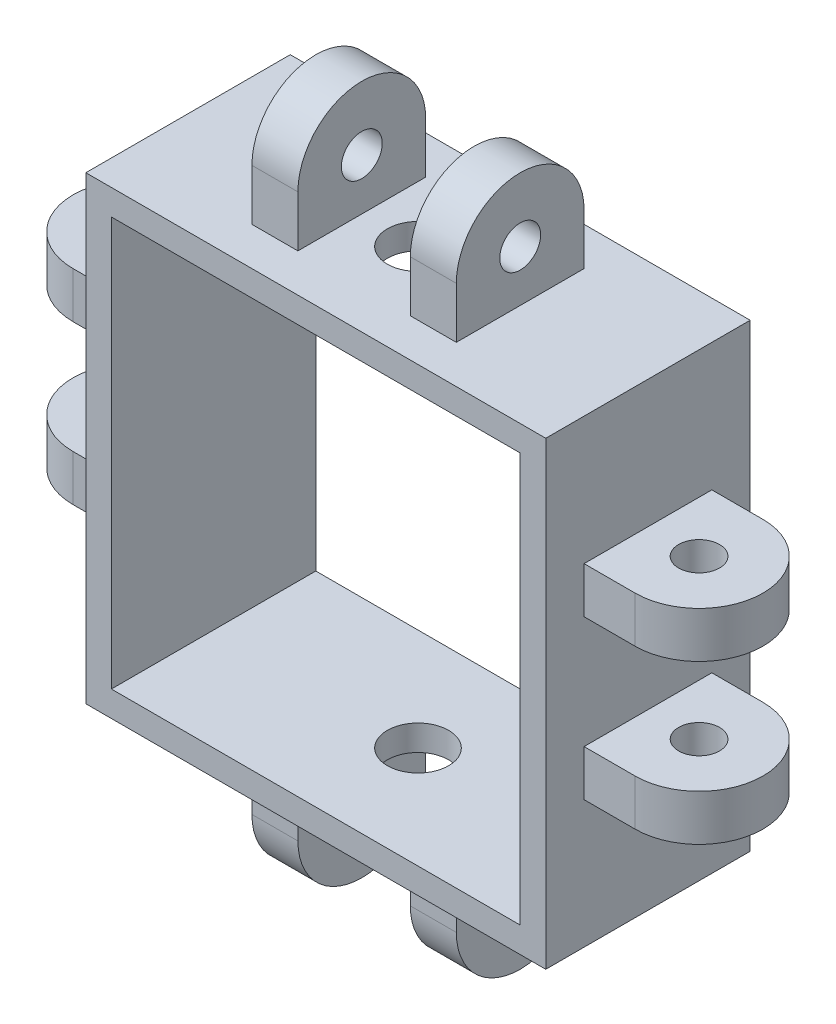
SolidWorks part; units mm, degrees
material "2024 合金"
ref_plane "前视基准面" through (0, 0, 0) normal (0, 0, 1) x (1, 0, 0)
ref_plane "上视基准面" through (0, 0, 0) normal (0, 1, 0) x (1, 0, 0)
ref_plane "右视基准面" through (0, 0, 0) normal (1, 0, 0) x (0, 0, -1)
sketch "草图1" plane through (0, 0, 0) normal (0, 0, 1) x (1, 0, 0)
  line L1 (-45, -45) -> (45, -45)
  line L2 (-45, -45) -> (-45, 45)
  line L3 (-45, 45) -> (45, 45)
  line L4 (45, -45) -> (45, 45)
  line L5 (-45, -45) -> (45, 45) construction
  line L6 (-45, 45) -> (45, -45) construction
  line L7 (-40, -40) -> (40, -40)
  line L8 (-40, -40) -> (-40, 40)
  line L9 (-40, 40) -> (40, 40)
  line L10 (40, -40) -> (40, 40)
  line L11 (-40, -40) -> (40, 40) construction
  line L12 (-40, 40) -> (40, -40) construction
  point P0 (0, 0)
  point P7 (0, 0)
  dimension "D1" = 90
  dimension "D2" = 90
  dimension "D3" = 80
  dimension "D4" = 80
extrude "凸台-拉伸1" add sketch "草图1" along normal blind 40
sketch "草图3" plane through (0, 45, 0) normal (0, 1, 0) x (1, 0, 0)
  line L0 (0, 0) -> (0, -20) construction
  line L1 (45, 0) -> (-45, 0) construction
  circle A0 centre (0, -20) radius 6
  dimension "D2" = 12
  dimension "D1" = 20
extrude "切除-拉伸2" cut sketch "草图3" against normal through all
sketch "草图4" plane through (0, -1.9977, 74.2652) normal (1, 0, 0) x (0, 0, -1)
  line L0 (41.7652, -43.0023) -> (41.7652, -53.0023)
  line L1 (66.7652, -53.0023) -> (66.7652, -43.0023)
  line L2 (66.7652, -43.0023) -> (41.7652, -43.0023)
  line L3 (54.2652, -42.5) -> (54.2652, -53.0023) construction
  line L4 (34.2652, -43.0023) -> (74.2652, -43.0023) construction
  arc A0 (41.7652, -53.0023) -> (66.7652, -53.0023) centre (54.2652, -53.0023) ccw
  circle A1 centre (54.2652, -53.0023) radius 4
  dimension "D3" = 8
  dimension "D1" = 25
  dimension "D2" = 10
extrude "凸台-拉伸2" add sketch "草图4" along normal blind 20 and the other way blind 20
sketch "草图5" plane through (0, 0, 7.5) normal (0, 0, -1) x (-1, 0, 0)
  line L0 (0, 0) -> (0, -60) construction
  line L1 (11, -45) -> (-11, -45)
  line L2 (11, -45) -> (11, -75)
  line L3 (11, -75) -> (-11, -75)
  line L4 (-11, -45) -> (-11, -75)
  line L5 (11, -45) -> (-11, -75) construction
  line L6 (11, -75) -> (-11, -45) construction
  line L7 (45, -45) -> (-45, -45) construction
  point P0 (0, -60)
  dimension "D1" = 22
  dimension "D2" = 30
extrude "切除-拉伸3" cut sketch "草图5" against normal through all
ref_plane "基准面1" through (0, 0, 0) normal (0, -1, 0) x (-1, 0, 0)
ref_plane "基准面2" through (0, 0, 0) normal (1, 0, 0) x (0, 0, -1)
ref_axis "基准轴1" through (0, 0, 42) along (0, 0, -1)
pattern_circular "阵列(圆周)3" count 4 over 360 about axis through (0, 0, 42) along (0, 0, -1) of "切除-拉伸3", "凸台-拉伸2"
